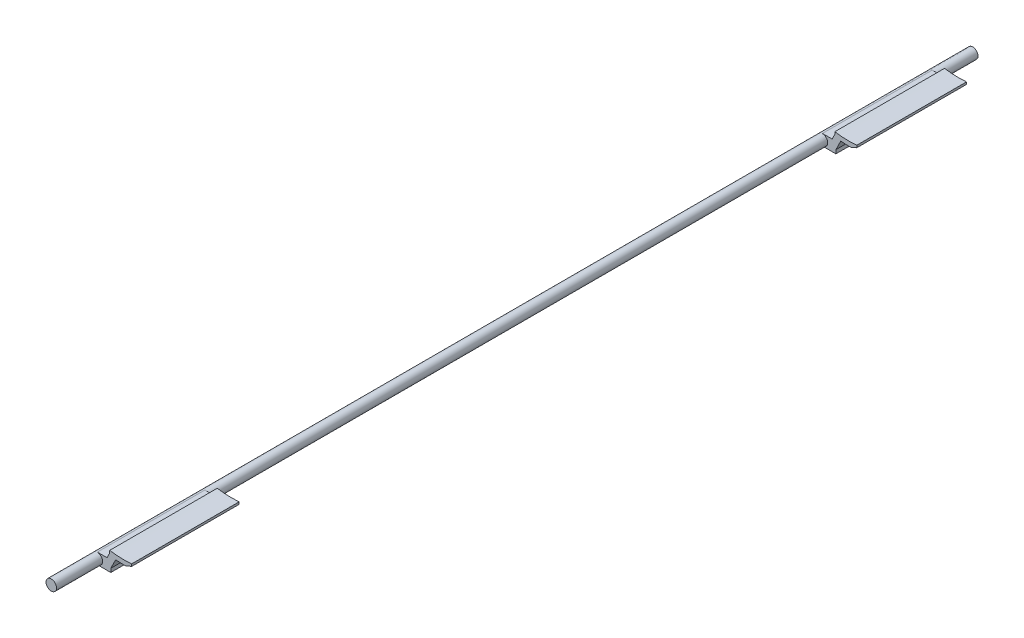
SolidWorks part; units mm, degrees
ref_plane "Front Plane" through (0, 0, 0) normal (0, 0, 1) x (1, 0, 0)
ref_plane "Top Plane" through (0, 0, 0) normal (0, 1, 0) x (1, 0, 0)
ref_plane "Right Plane" through (0, 0, 0) normal (1, 0, 0) x (0, 0, -1)
sketch "Sketch1" plane through (0, 0, 0) normal (0, 0, 1) x (1, 0, 0)
  line L0 (-6.3506, -38.9861) -> (-6.3506, -41.0112)
  line L1 (3.6494, -39.3311) -> (3.6494, -41.3392)
  arc A0 (-6.3506, -41.0112) -> (3.6494, -41.3392) centre (0, 0) ccw
  arc A1 (-6.3506, -38.9861) -> (3.6494, -39.3311) centre (0, 0) ccw
  circle A3 centre (0, 0) radius 39.5 construction
  circle A4 centre (0, 0) radius 41.5 construction
  point P4 (39.6866, 12.1334)
  point P9 (39.5, 0)
  dimension "D1" = 83
  dimension "D3" = 10
  dimension "D2" = 2
extrude "Boss-Extrude1" add sketch "Sketch1" along normal blind 49
chamfer "Chamfer1" distance 3 distance2 1 1 edges at (3.6494, -41.3392, 24.5) first distance on face at (-1.3556, -41.3265, 24.5)
ref_plane "Plane1" through (0, 0, 24.25) normal (0, 0, 1) x (1, 0, 0)
chamfer "Chamfer2" distance 1 distance2 3 1 edges at (-6.3506, -41.0112, 24.5) first distance on face at (-6.3506, -39.9987, 24.5)
sketch "Sketch4" plane through (-17.0904, -34.7255, 0) normal (-0.4416, -0.8972, 0) x (0.8972, -0.4416, 0)
  line L4 (14.9768, 49) -> (11.97, 49)
  line L5 (11.97, 49) -> (11.97, 0)
  line L6 (11.97, 0) -> (14.9768, 0)
  line L7 (14.9768, 0) -> (14.9768, 49)
  line L8 (14.9768, 49) -> (11.97, 49)
  line L9 (11.97, 49) -> (11.97, 0)
  line L10 (11.97, 0) -> (14.9768, 0)
  line L11 (14.9768, 0) -> (14.9768, 49)
  dimension "D1" = 0
extrude "Boss-Extrude2" add sketch "Sketch4" along normal blind 5
ref_plane "Plane2" through (-12, 0, 0) normal (1, 0, 0) x (0, 0, -1)
sketch "Sketch5" plane through (-12, 0, 0) normal (1, 0, 0) x (0, 0, -1)
  line L0 (0, 3.7614) -> (0, -3.7614) construction
  line L1 (0, -42.5038) -> (-49, -42.5038)
  line L2 (0, -42.5038) -> (0, -47.5038)
  line L3 (0, -47.5038) -> (-49, -47.5038)
  line L4 (-49, -42.5038) -> (-49, -47.5038)
  line L5 (-49, -44.4973) -> (-49, -40.0112) construction
  dimension "D1" = 5
extrude "Boss-Extrude3" add sketch "Sketch5" along normal up to vertex (6.1392 mm away) up to point (-5.8608, -45.825, 0)
sketch "Sketch6" plane through (0, 0, 0) normal (0, 0, -1) x (-1, 0, 0)
  line L0 (12, -47.5038) -> (12, -42.5038) construction
  circle A0 centre (12, -45.0038) radius 2.4
  dimension "D1" = 4.8
extrude "Boss-Extrude4" add sketch "Sketch6" along normal blind 350 and the other way blind 70
ref_plane "Plane4" through (0, 0, -281.5) normal (0, 0, -1) x (-1, 0, 0)
sketch "Sketch8" plane through (0, 0, -281.5) normal (0, 0, -1) x (-1, 0, 0)
  line L10 (12, -47.5038) -> (12, -47.4038)
  line L11 (12, -42.6038) -> (12, -42.5038)
  line L12 (12, -42.5038) -> (7.5774, -42.5038)
  line L13 (7.5774, -42.5038) -> (6.3506, -40.0112)
  line L14 (6.3506, -40.0112) -> (6.3506, -38.9861)
  line L15 (-3.6494, -39.3311) -> (-3.6494, -40.3392)
  line L16 (-3.6494, -40.3392) -> (-0.9293, -41.4896)
  line L17 (3.6529, -41.3389) -> (5.8608, -45.825)
  line L18 (5.8608, -45.825) -> (5.8608, -47.5038)
  line L19 (5.8608, -47.5038) -> (12, -47.5038)
  line L20 (12, -47.5038) -> (12, -47.4038)
  line L21 (12, -42.6038) -> (12, -42.5038)
  line L22 (12, -42.5038) -> (7.5774, -42.5038)
  line L23 (7.5774, -42.5038) -> (6.3506, -40.0112)
  line L24 (6.3506, -40.0112) -> (6.3506, -38.9861)
  line L25 (-3.6494, -39.3311) -> (-3.6494, -40.3392)
  line L26 (-3.6494, -40.3392) -> (-0.9293, -41.4896)
  line L27 (3.6529, -41.3389) -> (5.8608, -45.825)
  line L28 (5.8608, -45.825) -> (5.8608, -47.5038)
  line L29 (5.8608, -47.5038) -> (12, -47.5038)
  arc A3 (12, -42.6038) -> (12, -47.4038) centre (12, -45.0038) ccw
  arc A4 (-3.6494, -39.3311) -> (6.3506, -38.9861) centre (0, 0) ccw
  arc A5 (-0.9293, -41.4896) -> (3.6529, -41.3389) centre (0, 0) ccw
  arc A6 (12, -42.6038) -> (12, -47.4038) centre (12, -45.0038) ccw
  arc A7 (-3.6494, -39.3311) -> (6.3506, -38.9861) centre (0, 0) ccw
  arc A8 (-0.9293, -41.4896) -> (3.6529, -41.3389) centre (0, 0) ccw
  dimension "D1" = 0
extrude "Boss-Extrude5" add sketch "Sketch8" along normal blind 50
ref_plane "Plane6" through (0, 0, -140.75) normal (0, 0, -1) x (-1, 0, 0)
sketch "Sketch11" plane through (0, 0, -140.75) normal (0, 0, -1) x (-1, 0, 0)
  line L0 (14.7698, -46.3852) -> (14.1477, -46.075)
  line L1 (14.6472, -47.8751) -> (11.6077, -47.3715)
  circle A5 centre (12, -45.0038) radius 2.4 construction
  arc A6 (11.6077, -47.3715) -> (14.1477, -46.075) centre (12, -45.0038) ccw
  circle A7 centre (14.7698, -47.1352) radius 0.5
  arc A8 (14.6472, -47.8751) -> (14.7698, -46.3852) centre (14.7698, -47.1352) ccw
  dimension "D1" = 1
  dimension "D2" = 1.5
extrude "Boss-Extrude9" add sketch "Sketch11" along normal blind 2
